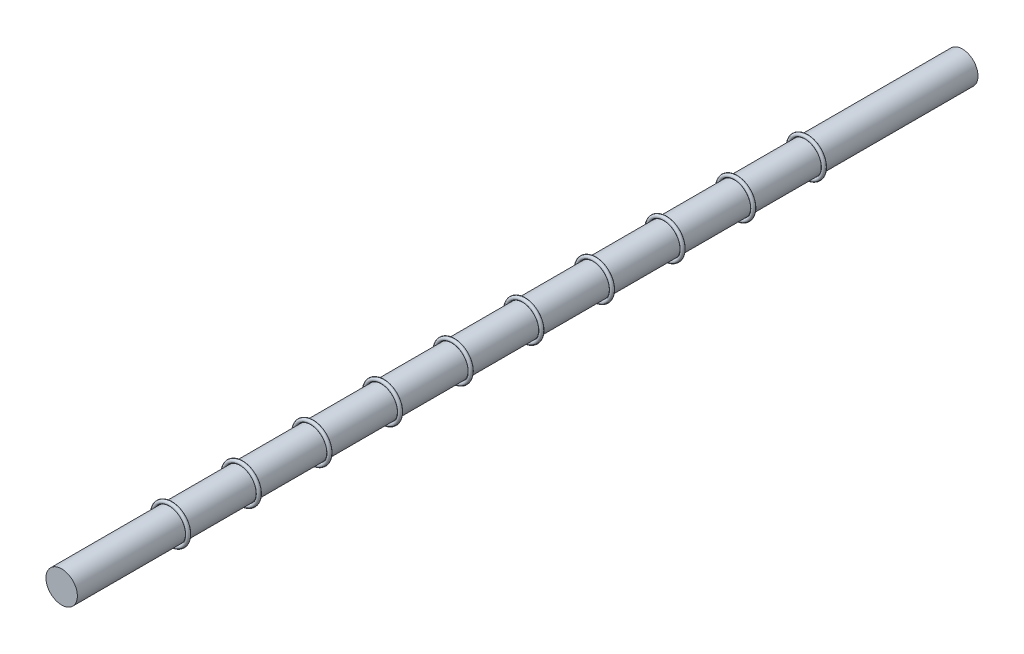
SolidWorks part; units mm, degrees
ref_plane "Front plane" through (0, 0, 0) normal (0, 0, 1) x (1, 0, 0)
ref_plane "Top plane" through (0, 0, 0) normal (0, 1, 0) x (1, 0, 0)
ref_plane "Right Plane" through (0, 0, 0) normal (1, 0, 0) x (0, 0, -1)
sketch "Sketch1" plane through (0, 0, 0) normal (0, 0, 1) x (1, 0, 0)
  circle A0 centre (0, 0) radius 4
  dimension "D1" = 8
extrude "Boss-Extrude1" add sketch "Sketch1" along normal blind 229.5
ref_plane "Plane1" through (0, 0, 196.25) normal (0, 0, 1) x (1, 0, 0)
sketch "Sketch2" [suppressed] plane through (0, 0, 196.25) normal (0, 0, 1) x (1, 0, 0)
  circle A0 centre (0, 0) radius 4.899
  circle A1 centre (0, 0) radius 4
  circle A2 centre (0, 0) radius 4 construction
  dimension "D1" = 9.798
extrude "Boss-Extrude2" [suppressed] add sketch "Sketch2" along normal mid plane 10 separate body
pattern_linear "LPattern1" [suppressed] count 6 spacing 35 of bodies 103
sketch "Sketch3" plane through (0, 0, 0) normal (0, 1, 0) x (1, 0, 0)
  line L0 (4, -229.5) -> (4, 0) construction
  line L1 (-4, -229.5) -> (4, -229.5) construction
  line L2 (4.4728, -183.75) -> (4.4728, -201.75) construction
  line L3 (0, -229.5) -> (0, 0) construction
  circle A0 centre (4.4728, -201.75) radius 0.4728
  circle A1 centre (4.4728, -183.75) radius 0.4728
  circle A2 centre (4.4728, -165.75) radius 0.4728
  circle A3 centre (4.4728, -147.75) radius 0.4728
  circle A4 centre (4.4728, -129.75) radius 0.4728
  circle A5 centre (4.4728, -111.75) radius 0.4728
  circle A6 centre (4.4728, -93.75) radius 0.4728
  circle A7 centre (4.4728, -75.75) radius 0.4728
  circle A8 centre (4.4728, -57.75) radius 0.4728
  circle A9 centre (4.4728, -39.75) radius 0.4728
  dimension "D1" = 0.4728
  dimension "D2" = 27.75
  dimension "D4" = 18
  dimension "D3" = 10
revolve "Revolve1" add sketch "Sketch3" angle 360 about L3
sketch "Sketch4" [suppressed] plane through (0, 0, 16.25) normal (0, 0, -1) x (-1, 0, 0)
  circle A0 centre (0, 0) radius 4 construction
  circle A1 centre (0, 0) radius 4.899
  circle A2 centre (0, 0) radius 4.899
  circle A3 centre (0, 0) radius 4
  dimension "D1" = 0
extrude "Boss-Extrude3" [suppressed] add sketch "Sketch4" along normal blind 4 from offset 6.2 separate body
equation "\"D1@Sketch2\"=2*sqr(4.5^2-3.5^2+4^2)"
equation "\"D1@Sketch3\"=0.47283"
